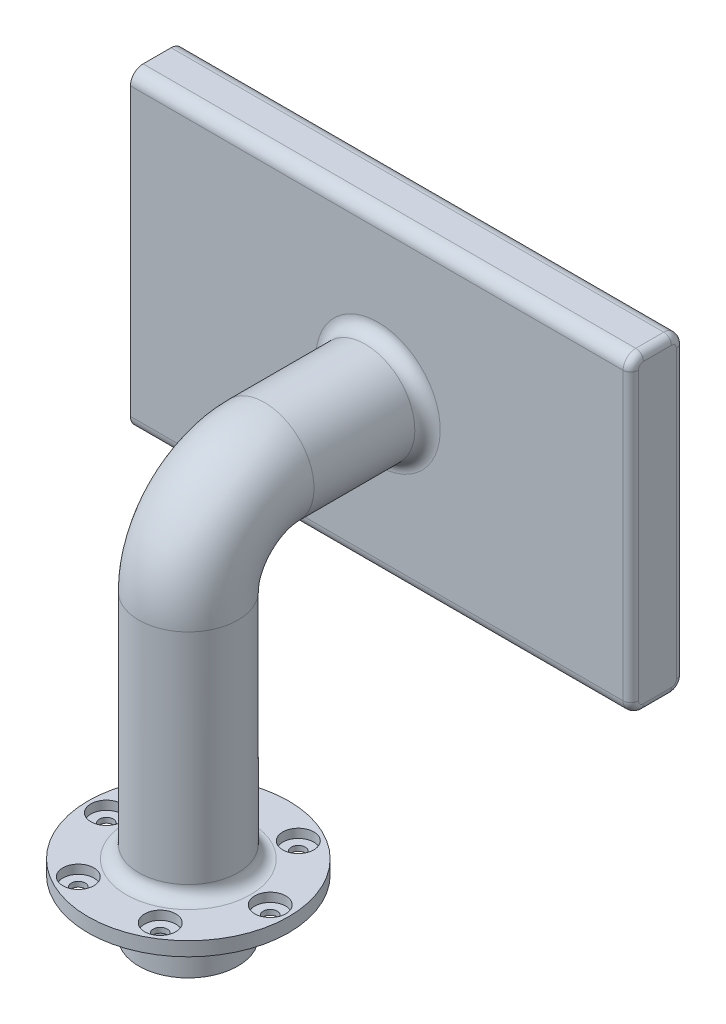
SolidWorks part; units mm, degrees
ref_plane "Front Plane" through (0, 0, 0) normal (0, 0, 1) x (1, 0, 0)
ref_plane "Top Plane" through (0, 0, 0) normal (0, 1, 0) x (1, 0, 0)
ref_plane "Right Plane" through (0, 0, 0) normal (1, 0, 0) x (0, 0, -1)
sketch "Sketch3" plane through (0, 0, 0) normal (1, 0, 0) x (0, 0, -1)
  line L0 (0, 0) -> (0, 52.5)
  line L1 (0, 0) -> (0, -52.5)
  line L2 (0, 0) -> (45.3348, 0) construction
  line L3 (21, -52.5) -> (21, -61.3564)
  line L5 (0, 52.5) -> (0, 61.3564)
  line L6 (0, 61.3564) -> (21, 61.3564)
  line L7 (21, 52.5) -> (21, 61.3564)
  line L8 (0, -52.5) -> (0, -61.3564)
  line L9 (0, -61.3564) -> (21, -61.3564)
  line L10 (21, 52.5) -> (19, 52.5)
  line L11 (19, 52.5) -> (19, 57.3564)
  line L12 (19, 57.3564) -> (4, 57.3564)
  line L13 (4, 57.3564) -> (4, -57.3564)
  line L14 (4, -57.3564) -> (19, -57.3564)
  line L15 (19, -57.3564) -> (19, -52.5)
  line L16 (19, -52.5) -> (21, -52.5)
  dimension "D2" = 15
  dimension "D1" = 105
  dimension "D3" = 2
  dimension "D4" = 4
  dimension "D5" = 15
  dimension "D6" = 2
  dimension "D7" = 4
  dimension "D8" = 4
extrude "Boss-Extrude1" add sketch "Sketch3" along normal mid plane 195
fillet "Fillet4" radius 5 2 edges at (0, 61.3564, -21) (0, 61.3564, 0)
fillet "Fillet5" radius 5 2 edges at (0, 57.3564, -19) (0, 57.3564, -4)
fillet "Fillet6" radius 5 4 edges at (0, -61.3564, -21) (0, -61.3564, 0) (0, -57.3564, -19) (0, -57.3564, -4)
ref_plane "Plane1" through (0, 0, 0) normal (1, 0, 0) x (0, 0, -1)
sketch "Sketch7" plane through (0, 0, 0) normal (0, 0, 1) x (1, 0, 0)
  circle A0 centre (0, 0) radius 19.5
  dimension "D1" = 39
sketch "Sketch8" plane through (0, 0, 0) normal (1, 0, 0) x (0, 0, -1)
  line L0 (0, 0) -> (-44.7052, 0)
  line L1 (0, 19.5) -> (0, -19.5) construction
  line L2 (-74.7052, -30) -> (-74.7052, -75)
  arc A0 (-44.7052, 0) -> (-74.7052, -30) centre (-44.7052, -30) ccw
  dimension "D1" = 30
  dimension "D2" = 45
sweep "Sweep1" add profiles "Sketch7" path "Sketch8"
sketch "Sketch10" plane through (0, -75, 0) normal (0, -1, 0) x (1, 0, 0)
  circle A3 centre (0, 74.7052) radius 19.5
  dimension "D1" = 39
extrude "Boss-Extrude2" add sketch "Sketch10" along normal blind 73
sketch "Sketch11" plane through (0, 0, 0) normal (1, 0, 0) x (0, 0, -1)
  line L0 (-74.7052, -148) -> (-74.7052, -124.1973) construction
  line L1 (-94.2052, -148) -> (-55.2052, -148) construction
  line L2 (-94.2052, -30) -> (-94.2052, -148) construction
  line L3 (-94.2052, -121.142) -> (-114.2052, -121.142)
  line L4 (-94.2052, -121.142) -> (-94.2052, -126.642)
  line L5 (-94.2052, -126.642) -> (-114.2052, -126.642)
  line L6 (-114.2052, -121.142) -> (-114.2052, -126.642)
  dimension "D1" = 5.5
  dimension "D2" = 20
revolve "Revolve1" add sketch "Sketch11" angle 360 about L0
fillet "Fillet8" radius 5 1 edges at (19.5, 0, 0)
fillet "Fillet9" radius 5 1 edges at (0, -121.142, 55.2052)
hole_wizard "CBORE for M5 Hex Head Bolt1" positions "3DSketch1" profile "Sketch12" counterbore size "M5" standard "ISO" end condition through all
sketch3d "3DSketch1"
  point P0 (-31.8244, -121.142, 75.1392)
sketch "Sketch12" plane through (-31.8244, -121.142, 75.1392) normal (1, 0, 0) x (0, 0, 1)
  line L0 (0, 0) -> (0, 26.858)
  line L1 (0, 26.858) -> (2.75, 26.858)
  line L3 (2.75, 26.858) -> (2.75, 3.5)
  line L4 (2.75, 3.5) -> (6.119, 3.5)
  line L5 (6.119, 3.5) -> (6.119, 0)
  line L7 (6.119, 0) -> (0, 0)
  line L11 (0, -6.35) -> (0, 107.95) construction
  dimension "Thru Hole Dia." = 5.5
  dimension "Thru Hole Depth" = 26.858
  dimension "C'Bore Dia." = 12.238
  dimension "C'Bore Depth" = 3.5
pattern_circular "CirPattern1" count 6 over 360 about axis through (0, -121.142, 74.7052) along (0, -1, 0) of "CBORE for M5 Hex Head Bolt1"
sketch "Sketch13" plane through (0, 0, -4) normal (0, 0, -1) x (-1, 0, 0)
  line L0 (-89.2558, 0) -> (87.4971, 0) construction
  text T0 "SMART METHODS"
extrude "Cut-Extrude1" cut sketch "Sketch13" against normal blind 0.4
sketch "Sketch14" plane through (97.5, 0, 0) normal (1, 0, 0) x (0, 0, -1)
  line L0 (21, 52.5) -> (21, -52.5)
  line L1 (21, -56.3564) -> (21, -52.5) construction
  line L2 (21, 52.5) -> (21, 56.3564) construction
  line L3 (16, 61.3564) -> (5, 61.3564) construction
  line L4 (0, 56.3564) -> (0, -56.3564) construction
  line L5 (5, -61.3564) -> (16, -61.3564) construction
  line L6 (21, -56.3564) -> (21, -52.5)
  line L7 (21, 52.5) -> (21, 56.3564)
  line L8 (16, 61.3564) -> (5, 61.3564)
  line L9 (0, 56.3564) -> (0, -56.3564)
  line L10 (5, -61.3564) -> (16, -61.3564)
  arc A0 (21, 56.3564) -> (16, 61.3564) centre (16, 56.3564) ccw construction
  arc A1 (5, 61.3564) -> (0, 56.3564) centre (5, 56.3564) ccw construction
  arc A2 (0, -56.3564) -> (5, -61.3564) centre (5, -56.3564) ccw construction
  arc A3 (16, -61.3564) -> (21, -56.3564) centre (16, -56.3564) ccw construction
  arc A4 (21, 56.3564) -> (16, 61.3564) centre (16, 56.3564) ccw
  arc A5 (5, 61.3564) -> (0, 56.3564) centre (5, 56.3564) ccw
  arc A6 (0, -56.3564) -> (5, -61.3564) centre (5, -56.3564) ccw
  arc A7 (16, -61.3564) -> (21, -56.3564) centre (16, -56.3564) ccw
extrude "Boss-Extrude3" add sketch "Sketch14" along normal blind 2
fillet "Fillet10" radius 3 8 edges at (99.5, -59.8919, -19.5355) (99.5, -61.3564, -10.5) (99.5, -59.8919, -1.4645) (99.5, 0, 0) (99.5, 59.8919, -1.4645) (99.5, 61.3564, -10.5) (99.5, 59.8919, -19.5355) (99.5, 0, -21)
fillet "Fillet11" radius 2 7 edges at (97.5, -55.9423, -17.4865) (97.5, -57.3564, -11.501) (97.5, -55.8919, -5.4645) (97.5, 55.9423, -17.4865) (97.5, 57.3564, -11.501) (97.5, 55.8919, -5.4645) (97.5, 0, -4)
